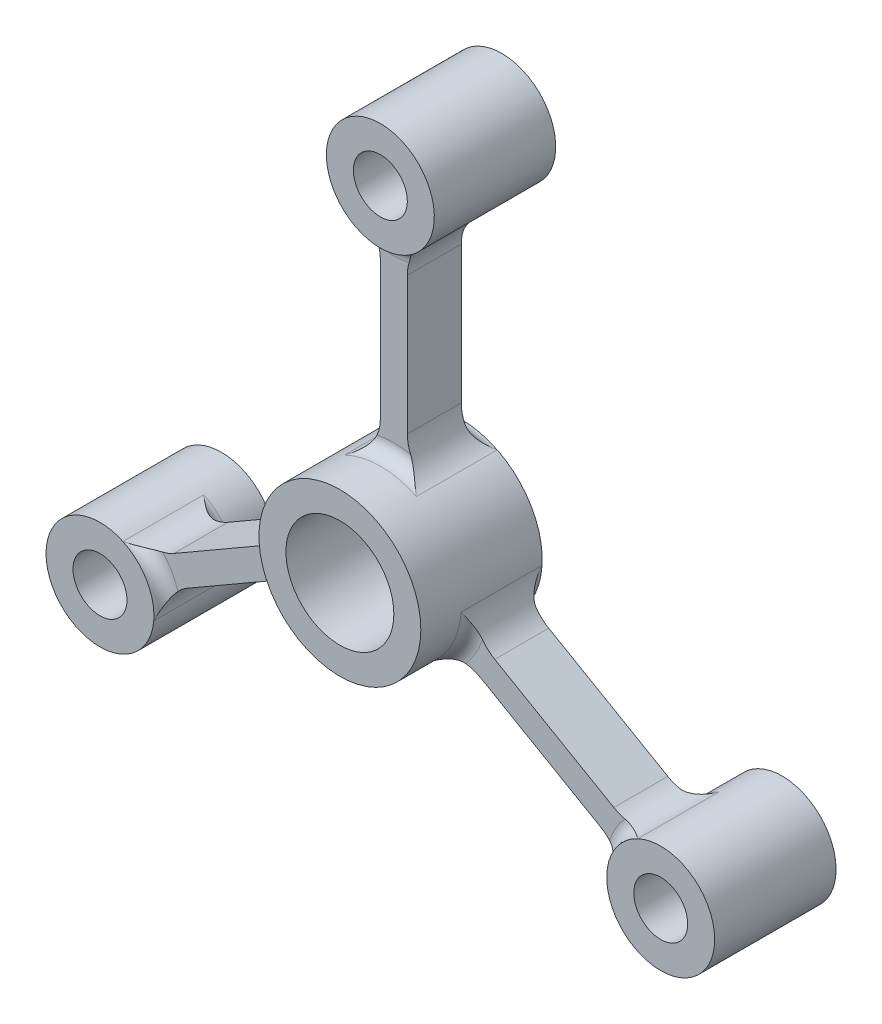
SolidWorks part; units mm, degrees
ref_plane "Plane1" through (0, 0, 0) normal (0, 0, 1) x (1, 0, 0)
ref_plane "Plane2" through (0, 0, 0) normal (0, 1, 0) x (1, 0, 0)
ref_plane "Plane3" through (0, 0, 0) normal (1, 0, 0) x (0, 0, -1)
other "Configuration Table"
sketch "Sketch2" plane through (0, 0, 0) normal (0, 0, 1) x (1, 0, 0)
  line L0 (0, 76.2) -> (0, 0) construction
  line L1 (0, 0) -> (65.9911, -38.1) construction
  line L2 (-65.9911, -38.1) -> (0, 0) construction
  line L3 (-3.175, 63.9033) -> (-3.175, 18.7836)
  line L4 (3.175, 63.9033) -> (3.175, 18.7836)
  line L5 (17.8545, -6.6421) -> (56.9294, -29.202)
  line L6 (14.6795, -12.1414) -> (53.7544, -34.7013)
  line L7 (-56.9294, -29.202) -> (-17.8545, -6.6421)
  line L8 (-53.7544, -34.7013) -> (-14.6795, -12.1414)
  arc A0 (17.8545, -6.6421) -> (3.175, 18.7836) centre (0, 0) ccw
  arc A1 (3.175, 63.9033) -> (-3.175, 63.9033) centre (0, 76.2) ccw
  arc A2 (53.7544, -34.7013) -> (56.9294, -29.202) centre (65.9911, -38.1) ccw
  arc A3 (-56.9294, -29.202) -> (-53.7544, -34.7013) centre (-65.9911, -38.1) ccw
  arc A4 (-14.6795, -12.1414) -> (14.6795, -12.1414) centre (0, 0) ccw
  arc A5 (-3.175, 18.7836) -> (-17.8545, -6.6421) centre (0, 0) ccw
  dimension "D1" = 38.1
  dimension "D2" = 25.4
  dimension "D3" = 120
  dimension "D4" = 120
  dimension "D5" = 76.2
  dimension "D6" = 3.175
extrude "Base-Extrude" add sketch "Sketch2" along normal blind 12.7
sketch "Sketch3" plane through (0, 0, 12.7) normal (0, 0, 1) x (1, 0, 0)
  circle A0 centre (0, 0) radius 19.05
extrude "Boss-Extrude1" add sketch "Sketch3" along normal blind 12.7
sketch "Sketch5" plane through (0, 0, 0) normal (0, 0, -1) x (-1, 0, 0)
  circle A0 centre (65.9911, -38.1) radius 12.7
  circle A1 centre (-65.9911, -38.1) radius 12.7
  circle A2 centre (0, 76.2) radius 12.7
extrude "Boss-Extrude2" add sketch "Sketch5" along normal blind 12.7
sketch "Sketch10" plane through (0, 0, 12.7) normal (0, 0, 1) x (1, 0, 0)
  circle A0 centre (-65.9911, -38.1) radius 12.7
extrude "Boss-Extrude3" add sketch "Sketch10" along normal blind 3.175
sketch "Sketch11" plane through (0, 0, 12.7) normal (0, 0, 1) x (1, 0, 0)
  circle A0 centre (65.9911, -38.1) radius 12.7
extrude "Boss-Extrude4" add sketch "Sketch11" along normal blind 3.175
sketch "Sketch12" plane through (0, 0, 12.7) normal (0, 0, 1) x (1, 0, 0)
  circle A0 centre (0, 76.2) radius 12.7
  dimension "D1" = 25.4
extrude "Boss-Extrude5" add sketch "Sketch12" along normal blind 3.175
sketch "Sketch7" plane through (0, 0, 0) normal (0, 0, -1) x (-1, 0, 0)
  circle A0 centre (0, 76.2) radius 6.35
  circle A1 centre (65.9911, -38.1) radius 6.35
  circle A2 centre (-65.9911, -38.1) radius 6.35
  dimension "D1" = 12.7
extrude "Cut-Extrude2" cut sketch "Sketch7" against normal through all and the other way blind 12.7
sketch "Sketch13" plane through (0, 0, 0) normal (0, 0, -1) x (-1, 0, 0)
  circle A0 centre (0, 0) radius 19.05
extrude "Boss-Extrude6" add sketch "Sketch13" along normal blind 3.175
sketch "Sketch4" plane through (0, 0, 25.4) normal (0, 0, 1) x (1, 0, 0)
  circle A0 centre (0, 0) radius 12.7
  dimension "D1" = 25.4
extrude "Cut-Extrude1" cut sketch "Sketch4" against normal through all
fillet "Fillet6" radius 9.525 6 edges at (3.175, 18.7836, 6.35) (-3.175, 18.7836, 6.35) (-17.8545, -6.6421, 6.35) (-14.6795, -12.1414, 6.35) (14.6795, -12.1414, 6.35) (17.8545, -6.6421, 6.35)
fillet "Fillet8" radius 3.175 6 edges at (-16.4978, -9.525, 12.7) (0, 19.05, 12.7) (-16.4978, -9.525, 0) (0, 19.05, 0) (16.4978, -9.525, 0) (16.4978, -9.525, 12.7)
fillet "Fillet9" radius 9.525 6 edges at (-56.9294, -29.202, 6.35) (-53.7544, -34.7013, 6.35) (-3.175, 63.9033, 6.35) (3.175, 63.9033, 6.35) (56.9294, -29.202, 6.35) (53.7544, -34.7013, 6.35)
fillet "Fillet10" radius 3.175 6 edges at (-54.9926, -31.75, 12.7) (-54.9926, -31.75, 0) (0, 63.5, 12.7) (0, 63.5, 0) (54.9926, -31.75, 0) (54.9926, -31.75, 12.7)
